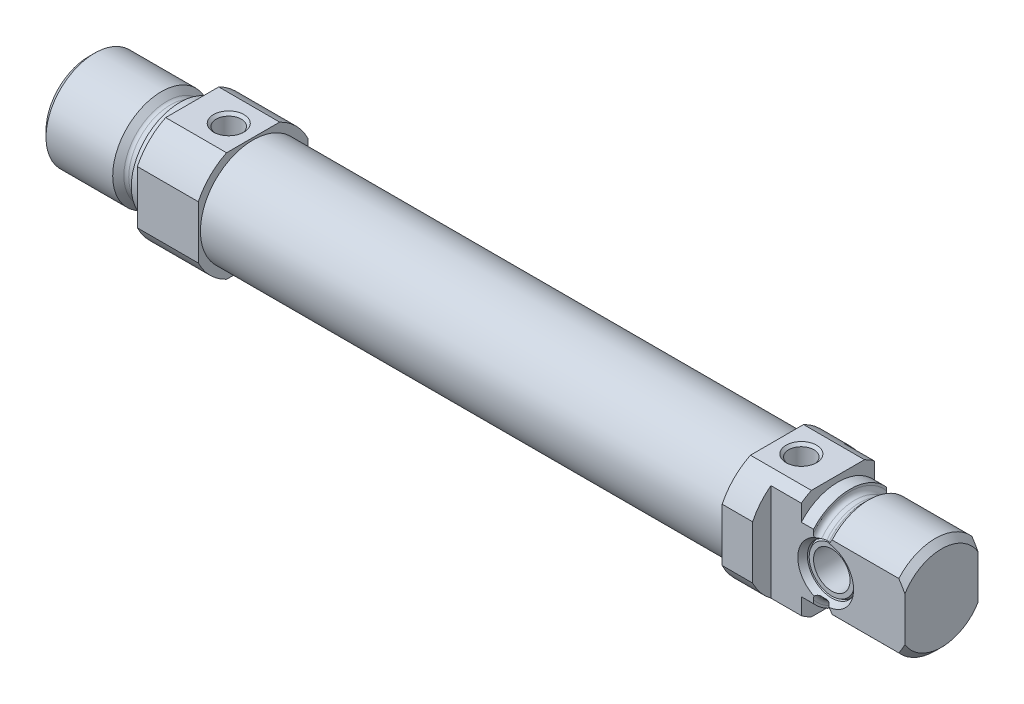
SolidWorks part; units mm, degrees
ref_plane "Front Plane" through (0, 0, 0) normal (0, 0, 1) x (1, 0, 0)
ref_plane "Top Plane" through (0, 0, 0) normal (0, 1, 0) x (1, 0, 0)
ref_plane "Right Plane" through (0, 0, 0) normal (1, 0, 0) x (0, 0, -1)
sketch "Sketch1" plane through (0, 0, 0) normal (0, 0, 1) x (1, 0, 0)
  line L0 (0, 0) -> (0, 7)
  line L1 (0, 7) -> (1, 8)
  line L2 (1, 8) -> (11.95, 8)
  line L3 (11.95, 8) -> (12.8657, 7.0843)
  line L4 (13.4314, 6.85) -> (14.2, 6.85)
  line L5 (15, 7.65) -> (15, 8)
  line L6 (15, 8) -> (17, 8)
  line L7 (17, 8) -> (17, 0)
  line L8 (17, 0) -> (0, 0)
  line L9 (17, 0) -> (0, 0) construction
  arc A0 (12.8657, 7.0843) -> (13.4314, 6.85) centre (13.4314, 7.65) ccw
  arc A1 (14.2, 6.85) -> (15, 7.65) centre (14.2, 7.65) ccw
revolve "Revolve1" add sketch "Sketch1" angle 360 about L9 reverse direction yes
cosmetic thread "Cosmetic Thread1" parameters "D1"=11.87, "D2"=14.16
ref_plane "Plane1" through (21.1, 0, 0) normal (1, 0, 0) x (0, 0, -1)
ref_plane "Plane2" through (9, 0, 0) normal (1, 0, 0) x (0, 0, -1)
ref_plane "Plane3" through (0, -11, 0) normal (0, 1, 0) x (1, 0, 0)
ref_plane "Plane4" through (0, 11, 0) normal (0, 1, 0) x (1, 0, 0)
ref_plane "Plane5" through (0, 0, 0) normal (0, 1, 0) x (1, 0, 0)
ref_plane "Plane6" through (0, 0, 0) normal (0, 1, 0) x (1, 0, 0)
ref_plane "Plane7" through (17, 0, 0) normal (1, 0, 0) x (0, 0, -1)
ref_plane "Plane8" through (17, 0, 0) normal (1, 0, 0) x (0, 0, -1)
ref_plane "Plane9" through (27, 0, 0) normal (1, 0, 0) x (0, 0, -1)
ref_plane "Plane10" through (17, 0, 0) normal (1, 0, 0) x (0, 0, -1)
ref_plane "Plane11" through (17, 0, 0) normal (1, 0, 0) x (0, 0, -1)
sketch "Sketch2" plane through (17, 0, 0) normal (1, 0, 0) x (0, 0, -1)
  line L0 (-4.3589, -9) -> (4.3589, -9)
  line L1 (9, -4.3589) -> (9, 4.3589)
  line L2 (4.3589, 9) -> (-4.3589, 9)
  line L3 (-9, 4.3589) -> (-9, -4.3589)
  arc A0 (-9, -4.3589) -> (-4.3589, -9) centre (0, 0) ccw
  arc A1 (4.3589, -9) -> (9, -4.3589) centre (0, 0) ccw
  arc A2 (9, 4.3589) -> (4.3589, 9) centre (0, 0) ccw
  arc A3 (-4.3589, 9) -> (-9, 4.3589) centre (0, 0) ccw
extrude "Boss-Extrude1" add sketch "Sketch2" along normal blind 10
ref_plane "Plane12" through (23, 0, 0) normal (1, 0, 0) x (0, 0, -1)
ref_plane "Plane13" through (0, 0, 0) normal (0, 0, 1) x (1, 0, 0)
ref_plane "Plane14" through (0, 0, -5.8) normal (0, 0, 1) x (1, 0, 0)
ref_plane "Plane15" through (0, 0, 0) normal (0, 1, 0) x (1, 0, 0)
ref_plane "Plane16" through (0, 4.5, 0) normal (0, 1, 0) x (1, 0, 0)
ref_plane "Plane17" through (0, 0, -6.6) normal (0, 0, 1) x (1, 0, 0)
ref_plane "Plane18" through (0, 0, 0) normal (0, 1, 0) x (1, 0, 0)
ref_plane "Plane19" through (0, 4.5, 0) normal (0, 1, 0) x (1, 0, 0)
ref_plane "Plane20" through (0, 5.493, -0.9686) normal (0, 0.9848, -0.1736) x (1, 0, 0)
ref_plane "Plane21" through (0, 4.0158, -0.7081) normal (0, 0.9848, -0.1736) x (1, 0, 0)
sketch "Sketch3" plane through (0, 0, 0) normal (0, 0, 1) x (1, 0, 0)
  line L0 (27, 0) -> (27, 8.65)
  line L1 (27, 8.65) -> (113, 8.65)
  line L2 (113, 8.65) -> (113, 0)
  line L3 (113, 0) -> (27, 0)
  line L4 (113, 0) -> (27, 0) construction
revolve "Revolve2" add sketch "Sketch3" angle 360 about L4 reverse direction yes
ref_plane "Plane22" through (113, 0, 0) normal (1, 0, 0) x (0, 0, -1)
sketch "Sketch4" plane through (113, 0, 0) normal (1, 0, 0) x (0, 0, -1)
  line L0 (-9, -9) -> (9, -9)
  line L1 (9, -9) -> (9, 9)
  line L2 (9, 9) -> (-9, 9)
  line L3 (-9, 9) -> (-9, -9)
extrude "Boss-Extrude2" add sketch "Sketch4" along normal blind 10
sketch "Sketch5" plane through (0, 0, 0) normal (0, 0, 1) x (1, 0, 0)
  line L0 (113, 20) -> (113, 10)
  line L1 (113, 10) -> (123, 10)
  line L2 (123, 10) -> (123, 20)
  line L3 (123, 20) -> (113, 20)
  line L4 (123, 0) -> (113, 0) construction
revolve "Cut-Revolve1" cut sketch "Sketch5" angle 360 about L4 reverse direction yes
ref_plane "Plane23" through (115.3, 0, 0) normal (1, 0, 0) x (0, 0, -1)
ref_plane "Plane24" through (117, 0, 0) normal (1, 0, 0) x (0, 0, -1)
ref_plane "Plane25" through (0, 0, 6.6) normal (0, 0, 1) x (1, 0, 0)
ref_plane "Plane26" through (0, 0, 0) normal (0, 1, 0) x (1, 0, 0)
ref_plane "Plane27" through (0, 4.5, 0) normal (0, 1, 0) x (1, 0, 0)
ref_plane "Plane28" through (0, 5.493, 0.9686) normal (0, 0.9848, 0.1736) x (1, 0, 0)
ref_plane "Plane29" through (0, 4.0158, 0.7081) normal (0, 0.9848, 0.1736) x (1, 0, 0)
ref_plane "Plane30" through (161, 0, 0) normal (1, 0, 0) x (0, 0, -1)
sketch "Sketch6" plane through (0, 0, 0) normal (0, 0, 1) x (1, 0, 0)
  line L0 (123, 0) -> (123, 8)
  line L1 (123, 8) -> (125, 8)
  line L2 (125, 8) -> (125, 7.65)
  line L3 (125.8, 6.85) -> (126.5686, 6.85)
  line L4 (127.1343, 7.0843) -> (128.05, 8)
  line L5 (128.05, 8) -> (139, 8)
  line L6 (139, 8) -> (140, 7)
  line L7 (140, 7) -> (140, 0)
  line L8 (140, 0) -> (123, 0)
  line L9 (140, 0) -> (123, 0) construction
  arc A0 (125, 7.65) -> (125.8, 6.85) centre (125.8, 7.65) ccw
  arc A1 (126.5686, 6.85) -> (127.1343, 7.0843) centre (126.5686, 7.65) ccw
revolve "Revolve3" add sketch "Sketch6" angle 360 about L9 reverse direction yes
cosmetic thread "Cosmetic Thread2" parameters "D1"=11.87, "D2"=14.16
ref_plane "Plane31" through (151, 0, 0) normal (1, 0, 0) x (0, 0, -1)
ref_plane "Plane32" through (161, 0, 0) normal (1, 0, 0) x (0, 0, -1)
ref_plane "Plane33" through (161, 0, 0) normal (1, 0, 0) x (0, 0, -1)
sketch "Sketch7" plane through (0, 0, 0) normal (0, 1, 0) x (1, 0, 0)
  line L0 (118, 18) -> (118, 6)
  line L1 (118, 6) -> (140, 6)
  line L2 (140, 6) -> (140, -6)
  line L3 (140, -6) -> (118, -6)
  line L4 (118, -6) -> (118, -18)
  line L5 (118, -18) -> (152, -18)
  line L6 (152, -18) -> (152, 18)
  line L7 (152, 18) -> (118, 18)
extrude "Cut-Extrude1" cut sketch "Sketch7" along normal blind 10 and the other way blind 10
ref_plane "Plane34" through (127, 0, 0) normal (1, 0, 0) x (0, 0, -1)
sketch "Sketch8" plane through (127, 0, 0) normal (1, 0, 0) x (0, 0, -1)
  line L0 (-6.2, 0) -> (-6.2, 4.6928)
  line L1 (-6.2, 4.6928) -> (-5, 4)
  line L2 (-5, 4) -> (-4.5, 4)
  line L3 (-4.5, 4) -> (-5, 3.7113)
  line L4 (-5, 3.7113) -> (-5, 3)
  line L5 (-5, 3) -> (5, 3)
  line L6 (5, 3) -> (5, 3.7113)
  line L7 (5, 3.7113) -> (4.5, 4)
  line L8 (4.5, 4) -> (5, 4)
  line L9 (5, 4) -> (6.2, 4.6928)
  line L10 (6.2, 4.6928) -> (6.2, 0)
  line L11 (6.2, 0) -> (-6.2, 0)
  line L12 (5, 0) -> (-6.2, 0) construction
revolve "Cut-Revolve2" cut sketch "Sketch8" angle 360 about L12 reverse direction yes
hole_wizard "Hole1" positions "Sketch10" profile "Sketch9" legacy
sketch "Sketch10" plane through (0, 9, 0) normal (0, 1, 0) x (1, 0, 0)
  point P0 (23, 0)
sketch "Sketch9" plane through (23, 9, 0) normal (1, 0, 0) x (0, 0, 1)
  line L0 (0, 0) -> (0, 9)
  line L1 (0, 9) -> (2.067, 9)
  line L2 (2.067, 9) -> (2.067, 0.433)
  line L3 (2.067, 0.433) -> (2.5, 0)
  line L4 (2.5, 0) -> (0, 0)
  line L5 (0, -6.4453) -> (0, 115.525) construction
  line L6 (-2.067, 0.433) -> (-2.5, 0) construction
  dimension "Diameter" = 4.134
  dimension "Depth" = 9
  dimension "C-Sink Angle" = 90
  dimension "C-Sink Diameter" = 5
cosmetic thread "Cosmetic Thread3" parameters "D1"=7, "D2"=5
hole_wizard "Hole2" positions "Sketch12" profile "Sketch11" legacy
sketch "Sketch12" plane through (0, 9, 0) normal (0, 1, 0) x (1, 0, 0)
  point P0 (117, 0)
sketch "Sketch11" plane through (117, 9, 0) normal (1, 0, 0) x (0, 0, 1)
  line L0 (0, 0) -> (0, 12.1934)
  line L1 (0, 12.1934) -> (2.067, 11)
  line L2 (2.067, 11) -> (2.067, 0.433)
  line L3 (2.067, 0.433) -> (2.5, 0)
  line L4 (2.5, 0) -> (0, 0)
  line L5 (0, -14.3089) -> (0, 102.4216) construction
  line L6 (0, 12.1934) -> (-2.067, 11) construction
  line L7 (-2.067, 0.433) -> (-2.5, 0) construction
  dimension "Diameter" = 4.134
  dimension "Depth" = 11
  dimension "C-Sink Diameter" = 5
  dimension "C-Sink Angle" = 90
  dimension "Drill Angle" = 120
cosmetic thread "Cosmetic Thread4" parameters "D1"=6, "D2"=5
sketch "Sketch13" plane through (0, 0, 0) normal (0, 0, 1) x (1, 0, 0)
  line L0 (-5, 0) -> (-5, 3)
  line L1 (-5, 3) -> (41.2, 3)
  line L2 (41.2, 3) -> (41.2, 8)
  line L3 (41.2, 8) -> (95.2, 8)
  line L4 (95.2, 8) -> (95.2, 0)
  line L5 (95.2, 0) -> (-5, 0)
  line L6 (95.2, 0) -> (-5, 0) construction
revolve "Cut-Revolve3" cut sketch "Sketch13" angle 360 about L6 reverse direction yes
ref_plane "Plane35" through (-5, 0, 0) normal (1, 0, 0) x (0, 0, -1)
ref_plane "Plane36" through (0, 9, 0) normal (0, 1, 0) x (1, 0, 0)
ref_plane "Plane37" through (8, 0, 0) normal (1, 0, 0) x (0, 0, -1)
ref_plane "Plane38" through (0, 0, 0) normal (1, 0, 0) x (0, 0, -1)
ref_plane "Plane39" through (17, 0, 0) normal (1, 0, 0) x (0, 0, -1)
ref_plane "Plane40" through (123, 0, 0) normal (1, 0, 0) x (0, 0, -1)
ref_plane "Plane41" through (17, 0, 0) normal (1, 0, 0) x (0, 0, -1)
ref_plane "Plane42" through (0, 9, 0) normal (0, 1, 0) x (1, 0, 0)
ref_plane "Plane43" through (36.5, 0, 0) normal (1, 0, 0) x (0, 0, -1)
ref_plane "Plane44" through (103.5, 0, 0) normal (1, 0, 0) x (0, 0, -1)
ref_plane "Plane45" through (0, 0, 0) normal (0, 0, 1) x (1, 0, 0)
ref_plane "Plane46" through (17, 0, 0) normal (1, 0, 0) x (0, 0, -1)
ref_plane "Plane47" through (0, 9, 0) normal (0, 1, 0) x (1, 0, 0)
ref_plane "Plane48" through (3, 0, 0) normal (1, 0, 0) x (0, 0, -1)
ref_plane "Plane49" through (0, 9, 0) normal (0, 1, 0) x (1, 0, 0)
ref_plane "FDT_FRONT XY" through (17, 0, 0) normal (1, 0, 0) x (0, 0, -1)
ref_plane "FDT_FRONT XZ" through (0, 0, 0) normal (0, -1, 0) x (-1, 0, 0)
ref_plane "FDT_FRONT YZ" through (0, 0, 0) normal (0, 0, -1) x (-1, 0, 0)
ref_axis "FDT_FRONT X" through (17, 0, 80.9) along (0, 0, -1)
ref_axis "FDT_FRONT Y" through (17, -50, 0) along (0, 1, 0)
ref_axis "FDT_FRONT Z" through (80.9, 0, 0) along (-1, 0, 0)
sketch3d "FDT_FRONT"
  point P0 (17, 0, 0)
ref_plane "FDT_QSFRONT XY" through (0, 9, 0) normal (0, 1, 0) x (1, 0, 0)
ref_plane "FDT_QSFRONT XZ" through (23, 0, 0) normal (-1, 0, 0) x (0, 0, 1)
ref_plane "FDT_QSFRONT YZ" through (0, 0, 0) normal (0, 0, 1) x (1, 0, 0)
ref_axis "FDT_QSFRONT X" through (23, 9, -50) along (0, 0, 1)
ref_axis "FDT_QSFRONT Y" through (-80.9, 9, 0) along (1, 0, 0)
ref_axis "FDT_QSFRONT Z" through (23, 50, 0) along (0, -1, 0)
sketch3d "FDT_QSFRONT"
  point P0 (23, 9, 0)
ref_plane "FDT_QSREAR XY" through (0, 9, 0) normal (0, 1, 0) x (1, 0, 0)
ref_plane "FDT_QSREAR XZ" through (117, 0, 0) normal (-1, 0, 0) x (0, 0, 1)
ref_plane "FDT_QSREAR YZ" through (0, 0, 0) normal (0, 0, 1) x (1, 0, 0)
ref_axis "FDT_QSREAR X" through (117, 9, -50) along (0, 0, 1)
ref_axis "FDT_QSREAR Y" through (-80.9, 9, 0) along (1, 0, 0)
ref_axis "FDT_QSREAR Z" through (117, 50, 0) along (0, -1, 0)
sketch3d "FDT_QSREAR"
  point P0 (117, 9, 0)
ref_plane "FDT_REAR XY" through (123, 0, 0) normal (-1, 0, 0) x (0, 0, 1)
ref_plane "FDT_REAR XZ" through (0, 0, 0) normal (0, 1, 0) x (1, 0, 0)
ref_plane "FDT_REAR YZ" through (0, 0, 0) normal (0, 0, -1) x (-1, 0, 0)
ref_axis "FDT_REAR X" through (123, 0, 80.9) along (0, 0, -1)
ref_axis "FDT_REAR Y" through (123, 50, 0) along (0, -1, 0)
ref_axis "FDT_REAR Z" through (-80.9, 0, 0) along (1, 0, 0)
sketch3d "FDT_REAR"
  point P0 (123, 0, 0)
ref_plane "FDT_SMBR1 XY" through (36.5, 0, 0) normal (-1, 0, 0) x (0, 0, 1)
ref_plane "FDT_SMBR1 XZ" through (0, 0, 0) normal (0, -1, 0) x (-1, 0, 0)
ref_plane "FDT_SMBR1 YZ" through (0, 0, 0) normal (0, 0, 1) x (1, 0, 0)
ref_axis "FDT_SMBR1 X" through (36.5, 0, -80.9) along (0, 0, 1)
ref_axis "FDT_SMBR1 Y" through (36.5, -50, 0) along (0, 1, 0)
ref_axis "FDT_SMBR1 Z" through (-80.9, 0, 0) along (1, 0, 0)
sketch3d "FDT_SMBR1"
  point P0 (36.5, 0, 0)
ref_plane "FDT_SMBR2 XY" through (103.5, 0, 0) normal (-1, 0, 0) x (0, 0, 1)
ref_plane "FDT_SMBR2 XZ" through (0, 0, 0) normal (0, -1, 0) x (-1, 0, 0)
ref_plane "FDT_SMBR2 YZ" through (0, 0, 0) normal (0, 0, 1) x (1, 0, 0)
ref_axis "FDT_SMBR2 X" through (103.5, 0, -80.9) along (0, 0, 1)
ref_axis "FDT_SMBR2 Y" through (103.5, -50, 0) along (0, 1, 0)
ref_axis "FDT_SMBR2 Z" through (-80.9, 0, 0) along (1, 0, 0)
sketch3d "FDT_SMBR2"
  point P0 (103.5, 0, 0)
ref_plane "FDT_SWIVELAXIS XY" through (0, 0, 0) normal (0, 0, 1) x (1, 0, 0)
ref_plane "FDT_SWIVELAXIS XZ" through (0, 0, 0) normal (0, -1, 0) x (-1, 0, 0)
ref_plane "FDT_SWIVELAXIS YZ" through (127, 0, 0) normal (1, 0, 0) x (0, 0, -1)
ref_axis "FDT_SWIVELAXIS X" through (-80.9, 0, 0) along (1, 0, 0)
ref_axis "FDT_SWIVELAXIS Y" through (127, -50, 0) along (0, 1, 0)
ref_axis "FDT_SWIVELAXIS Z" through (127, 0, 80.9) along (0, 0, -1)
sketch3d "FDT_SWIVELAXIS"
  point P0 (127, 0, 0)
ref_plane "NUT XY" through (8, 0, 0) normal (1, 0, 0) x (0, 0, -1)
ref_plane "NUT XZ" through (0, 0, 0) normal (0, -1, 0) x (-1, 0, 0)
ref_plane "NUT YZ" through (0, 0, 0) normal (0, 0, -1) x (-1, 0, 0)
ref_axis "NUT X" through (8, 0, 80.9) along (0, 0, -1)
ref_axis "NUT Y" through (8, -50, 0) along (0, 1, 0)
ref_axis "NUT Z" through (80.9, 0, 0) along (-1, 0, 0)
sketch3d "NUT"
  point P0 (8, 0, 0)
ref_plane "ZR XY" through (0, 0, 0) normal (-1, 0, 0) x (0, 0, 1)
ref_plane "ZR XZ" through (0, 0, 0) normal (0, 1, 0) x (1, 0, 0)
ref_plane "ZR YZ" through (0, 0, 0) normal (0, 0, -1) x (-1, 0, 0)
ref_axis "ZR X" through (0, 0, 80.9) along (0, 0, -1)
ref_axis "ZR Y" through (0, 50, 0) along (0, -1, 0)
ref_axis "ZR Z" through (-80.9, 0, 0) along (1, 0, 0)
sketch3d "ZR"
  point P0 (0, 0, 0)
ref_plane "ZYL XY" through (17, 0, 0) normal (1, 0, 0) x (0, 0, -1)
ref_plane "ZYL XZ" through (0, 0, 0) normal (0, -1, 0) x (-1, 0, 0)
ref_plane "ZYL YZ" through (0, 0, 0) normal (0, 0, -1) x (-1, 0, 0)
ref_axis "ZYL X" through (17, 0, 80.9) along (0, 0, -1)
ref_axis "ZYL Y" through (17, -50, 0) along (0, 1, 0)
ref_axis "ZYL Z" through (80.9, 0, 0) along (-1, 0, 0)
sketch3d "ZYL"
  point P0 (17, 0, 0)
